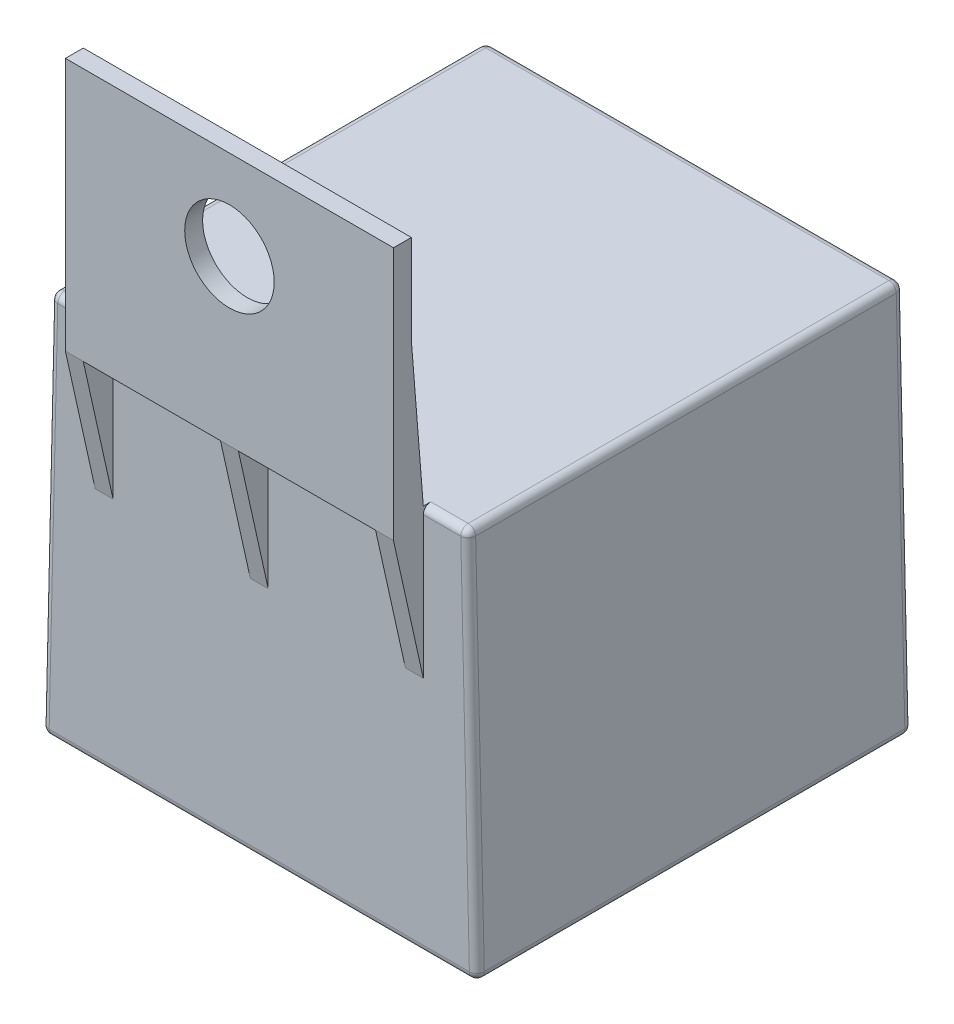
SolidWorks part; units mm, degrees
ref_plane "前视基准面" through (0, 0, 0) normal (0, 0, 1) x (1, 0, 0)
ref_plane "上视基准面" through (0, 0, 0) normal (0, 1, 0) x (1, 0, 0)
ref_plane "右视基准面" through (0, 0, 0) normal (1, 0, 0) x (0, 0, -1)
sketch "Sketch1" plane through (0, 0, 0) normal (0, 1, 0) x (1, 0, 0)
  line L1 (-14.6, 14.6) -> (14.6, 14.6)
  line L2 (-14.6, 14.6) -> (-14.6, -14.6)
  line L3 (-14.6, -14.6) -> (14.6, -14.6)
  line L4 (14.6, 14.6) -> (14.6, -14.6)
  line L5 (-14.6, 14.6) -> (14.6, -14.6) construction
  line L6 (-14.6, -14.6) -> (14.6, 14.6) construction
  point P0 (0, 0)
  dimension "D1" = 29.2
  dimension "D2" = 29.2
ref_plane "Plane1" through (0, 26, 0) normal (0, 1, 0) x (1, 0, 0)
sketch "Sketch3" plane through (0, 26, 0) normal (0, 1, 0) x (1, 0, 0)
  line L0 (-14.6, -14.6) -> (14.6, 14.6) construction
  line L1 (-14, -14.6) -> (14, -14.6)
  line L2 (-14, -14.6) -> (-14, 14.6)
  line L3 (-14, 14.6) -> (14, 14.6)
  line L4 (14, -14.6) -> (14, 14.6)
  line L5 (-14, -14.6) -> (14, 14.6) construction
  line L6 (-14, 14.6) -> (14, -14.6) construction
  line L7 (-14.6, 14.6) -> (14.6, 14.6) construction
  point P0 (0, 0)
  dimension "D1" = 28
loft "Loft1" add profiles "Sketch3", "Sketch1" connector at (14, 26, 14.6) connector at (14.6, 0, 14.6)
sketch "Sketch6" plane through (0, 0, 14.6) normal (0, 0, 1) x (1, 0, 0)
  line L1 (-11, 42) -> (11, 42)
  line L2 (-11, 42) -> (-11, 25)
  line L3 (-11, 25) -> (11, 25)
  line L4 (11, 42) -> (11, 25)
  line L5 (-11, 42) -> (11, 25) construction
  line L6 (-11, 25) -> (11, 42) construction
  line L8 (-14.6, 0) -> (14.6, 0) construction
  point P0 (0, 33.5)
  point P5 (-10.2189, 23.7384)
  point P6 (0, 0)
  dimension "D1" = 22
  dimension "D2" = 17
  dimension "D3" = 42
extrude "Boss-Extrude1" add sketch "Sketch6" along normal blind 2
sketch "Sketch7" plane through (-11, 0, 0) normal (-1, 0, 0) x (0, 0, 1)
  line L0 (16.6, 25) -> (14.6, 16)
  line L1 (14.6, 26) -> (14.6, 0) construction
  line L2 (16.6, 25) -> (14.6, 25) construction
  dimension "D1" = 9
rib "Rib1" sketch "Sketch7" sketch "Sketch7" thickness 1.2 extrusion direction parallel to sketch draft on no parameters "D1"=1.2
sketch "Sketch8" plane through (0, 0, 0) normal (1, 0, 0) x (0, 0, -1)
  line L0 (-16.6, 25) -> (-14.6, 16)
rib "Rib3" sketch "Sketch8" sketch "Sketch8" thickness 1.2 extrusion direction parallel to sketch draft on no parameters "D1"=1.2
mirror "Mirror1" about plane through (0, 0, 0) normal (1, 0, 0) of "Rib1"
sketch "Sketch9" plane through (0, 0, 14.6) normal (0, 0, -1) x (-1, 0, 0)
  line L0 (16.0601, 26) -> (-16.0601, 26) construction
  line L1 (-11, 42) -> (11.0488, 42)
  line L2 (-11, 42) -> (-11, 26)
  line L3 (-11, 26) -> (11.0488, 26)
  line L4 (11.0488, 42) -> (11.0488, 26)
extrude "Cut-Extrude1" cut sketch "Sketch9" against normal blind 0.8
sketch "Sketch11" plane through (-11, 0, 0) normal (-1, 0, 0) x (0, 0, 1)
  line L0 (14.6, 26) -> (15.4, 36)
  line L1 (16.0601, 26) -> (-16.0601, 26) construction
  line L2 (14.6, 26) -> (14.6, 0) construction
  line L3 (15.4, 26) -> (15.4, 42) construction
  dimension "D1" = 10
rib "Rib4" sketch "Sketch11" sketch "Sketch11" thickness 1.2 extrusion direction parallel to sketch draft on no parameters "D1"=1.2
mirror "Mirror2" about plane through (0, 0, 0) normal (1, 0, 0) of "Rib4"
sketch "Sketch12" plane through (0, 0, 15.4) normal (0, 0, -1) x (-1, 0, 0)
  line L0 (11, 42) -> (-11, 42) construction
  circle A0 centre (0, 36) radius 3
  point P4 (0, 0)
  dimension "D2" = 6
  dimension "D1" = 6
extrude "Cut-Extrude2" cut sketch "Sketch12" against normal up to next
fillet "Fillet1" radius 0.8 3 edges at (0, 26, 15.4) (5.2, 25, 14.6) (-5.2, 25, 14.6)
fillet "Fillet2" radius 0.5 14 edges
